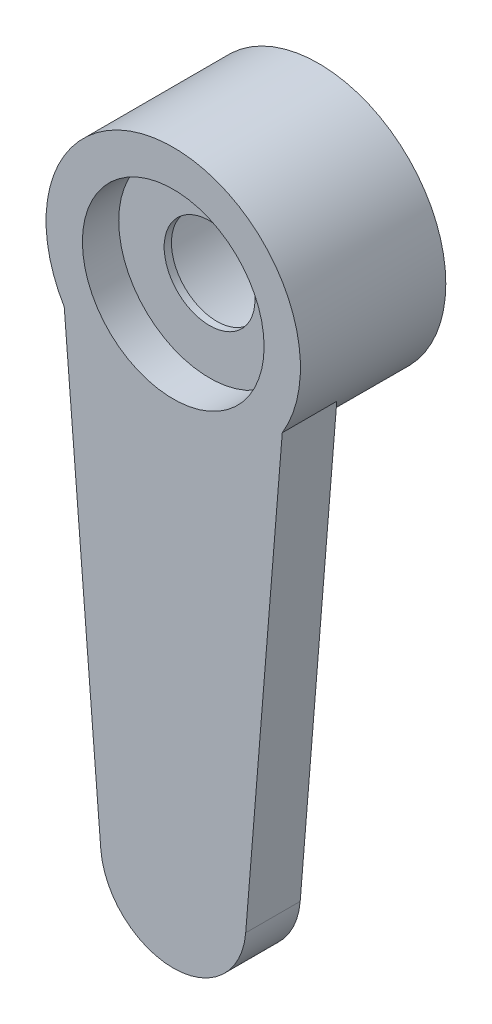
SolidWorks part; units mm, degrees
material "ABS"
ref_plane "Front" through (0, 0, 0) normal (0, 0, 1) x (1, 0, 0)
ref_plane "Top" through (0, 0, 0) normal (0, 1, 0) x (1, 0, 0)
ref_plane "Right" through (0, 0, 0) normal (1, 0, 0) x (0, 0, -1)
sketch "Sketch1" plane through (0, 0, 0) normal (0, 0, 1) x (1, 0, 0)
  circle A0 centre (0, 0) radius 3.5
  circle A1 centre (0, 0) radius 2.5
  dimension "D1" = 7
  dimension "D2" = 5
extrude "Boss-Extrude1" add sketch "Sketch1" along normal blind 2.8
sketch "Sketch2" plane through (0, 0, 2.8) normal (0, 0, 1) x (1, 0, 0)
  circle A0 centre (0, 0) radius 3.5
  circle A1 centre (0, 0) radius 1.25
  dimension "D1" = 2.5
extrude "Boss-Extrude2" add sketch "Sketch2" along normal blind 0.2
sketch "Sketch3" plane through (0, 0, 3) normal (0, 0, 1) x (1, 0, 0)
  circle A0 centre (0, 0) radius 3.5
  circle A1 centre (0, 0) radius 2.5
  dimension "D1" = 5
extrude "Boss-Extrude3" add sketch "Sketch3" along normal blind 1
sketch "Sketch4" plane through (0, 0, 4) normal (0, 0, 1) x (1, 0, 0)
  line L0 (-3, -1.8028) -> (-1.9935, -14.2233)
  line L1 (3, -1.8028) -> (1.9935, -14.2233)
  circle A0 centre (0, 0) radius 3.5 construction
  arc A1 (-1.9935, -14.2233) -> (1.9935, -14.2233) centre (0, -14.0618) ccw
  arc A2 (-3, -1.8028) -> (3, -1.8028) centre (0, 0) ccw
  dimension "D2" = 16.0618
  dimension "D3" = 2
  dimension "D1" = 6
extrude "Boss-Extrude4" add sketch "Sketch4" against normal blind 1.5
